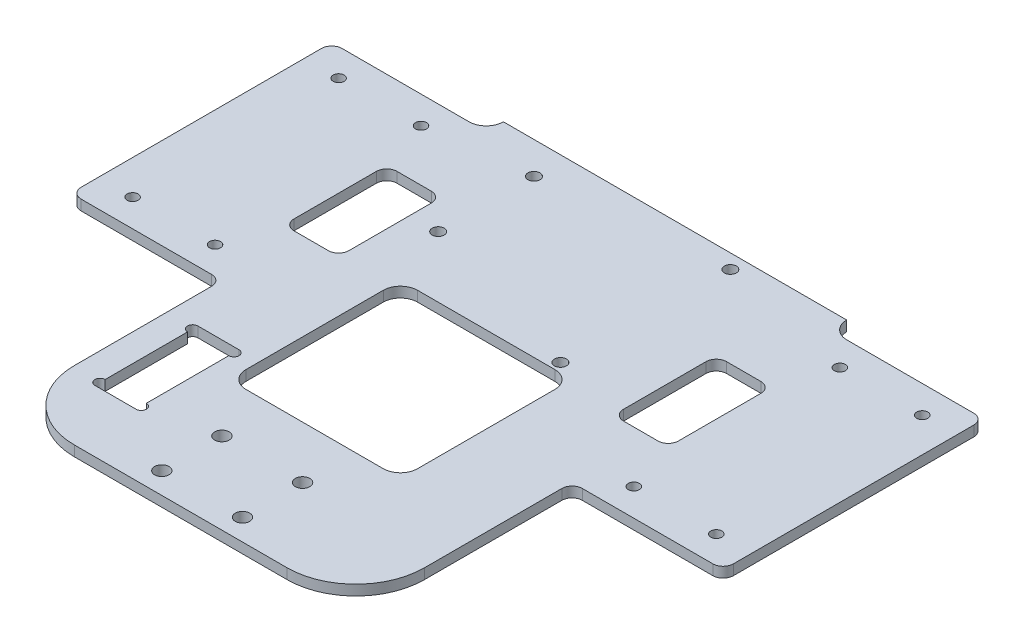
SolidWorks part; units mm, degrees
ref_plane "前视基准面" through (0, 0, 0) normal (0, 0, 1) x (1, 0, 0)
ref_plane "上视基准面" through (0, 0, 0) normal (0, 1, 0) x (1, 0, 0)
ref_plane "右视基准面" through (0, 0, 0) normal (1, 0, 0) x (0, 0, -1)
other "Configuration Table"
sketch "草图1" plane through (0, 0, 0) normal (0, 1, 0) x (1, 0, 0)
  line L0 (-31, 0) -> (31, 0)
  line L1 (-95, 66) -> (-95, 136)
  line L2 (-92, 139) -> (92, 139)
  line L3 (95, 136) -> (95, 66)
  line L4 (-11.75, 6.25) -> (11.75, 6.25) construction
  line L5 (0, 0) -> (0, 71) construction
  line L6 (0, 71) -> (-61, 71) construction
  line L7 (-53, 116) -> (-43, 116)
  line L8 (-56, 113) -> (-56, 89)
  line L9 (-53, 86) -> (-43, 86)
  line L11 (-40, 113) -> (-40, 89)
  line L12 (40, 113) -> (40, 89)
  line L13 (53, 86) -> (43, 86)
  line L14 (56, 113) -> (56, 89)
  line L15 (53, 116) -> (43, 116)
  line L16 (-92, 63) -> (-54, 63)
  line L19 (54, 63) -> (92, 63)
  line L20 (51, 20) -> (51, 60)
  line L21 (-51, 20) -> (-51, 60)
  line L23 (-20, 89) -> (20, 89)
  line L24 (-25, 84) -> (-25, 44)
  line L25 (-20, 39) -> (20, 39)
  line L26 (25, 84) -> (25, 44)
  circle A0 centre (-11.75, 23.75) radius 2.1
  circle A1 centre (11.75, 23.75) radius 2.1
  circle A2 centre (11.75, 6.25) radius 2.1
  circle A3 centre (-11.75, 6.25) radius 2.1
  circle A4 centre (-61, 71) radius 1.6
  circle A5 centre (-61, 131) radius 1.6
  circle A6 centre (-85, 131) radius 1.6
  circle A7 centre (-85, 71) radius 1.6
  arc A8 (-43, 116) -> (-40, 113) centre (-43, 113) cw
  arc A9 (-43, 86) -> (-40, 89) centre (-43, 89) ccw
  arc A10 (-56, 89) -> (-53, 86) centre (-53, 89) ccw
  arc A11 (-53, 116) -> (-56, 113) centre (-53, 113) ccw
  arc A12 (53, 116) -> (56, 113) centre (53, 113) cw
  arc A13 (56, 89) -> (53, 86) centre (53, 89) cw
  arc A14 (43, 86) -> (40, 89) centre (43, 89) cw
  arc A15 (43, 116) -> (40, 113) centre (43, 113) ccw
  circle A16 centre (85, 71) radius 1.6
  circle A17 centre (85, 131) radius 1.6
  circle A18 centre (61, 131) radius 1.6
  circle A19 centre (61, 71) radius 1.6
  arc A20 (92, 63) -> (95, 66) centre (92, 66) ccw
  arc A21 (92, 139) -> (95, 136) centre (92, 136) cw
  arc A22 (-95, 136) -> (-92, 139) centre (-92, 136) cw
  arc A23 (-92, 63) -> (-95, 66) centre (-92, 66) cw
  arc A32 (54, 63) -> (51, 60) centre (54, 60) ccw
  arc A33 (-54, 63) -> (-51, 60) centre (-54, 60) cw
  arc A34 (20, 89) -> (25, 84) centre (20, 84) cw
  arc A35 (20, 39) -> (25, 44) centre (20, 44) ccw
  arc A36 (-25, 44) -> (-20, 39) centre (-20, 44) ccw
  arc A37 (-20, 89) -> (-25, 84) centre (-20, 84) ccw
  arc A38 (31, 0) -> (51, 20) centre (31, 20) ccw
  arc A39 (-31, 0) -> (-51, 20) centre (-31, 20) cw
  point P1 (0, 0)
  point P4 (0, 6.25)
  point P32 (-40, 116)
  point P37 (-56, 86)
  point P40 (-56, 116)
  point P61 (56, 116)
  point P62 (56, 86)
  point P63 (40, 116)
  point P68 (0, 89)
  point P69 (0, 139)
  point P70 (25, 64)
  point P76 (95, 139)
  point P79 (-95, 139)
  point P84 (51, 63)
  point P88 (-51, 63)
  point P92 (25, 89)
  point P99 (-25, 89)
  point P102 (51, 0)
  point P105 (-51, 0)
  dimension "D1" = 4.2
  dimension "D4" = 17.5
  dimension "D5" = 3.2
  dimension "D15" = 3
  dimension "D22" = 3
  dimension "D23" = 75
  dimension "D24" = 50
  dimension "D25" = 3
  dimension "D20" = 102
  dimension "D26" = 5
  dimension "D27" = 20
  dimension "D2" = 23.5
  dimension "D3" = 6.25
  dimension "D6" = 24
  dimension "D7" = 60
  dimension "D8" = 61
  dimension "D9" = 102
  dimension "D10" = 190
  dimension "D11" = 30
  dimension "D12" = 16
  dimension "D13" = 0
  dimension "D14" = 40
  dimension "D16" = 8
  dimension "D17" = 8
  dimension "D18" = 139
  dimension "D19" = 8
  dimension "D21" = 15
extrude "凸台-拉伸1" add sketch "草图1" along normal blind 3
sketch "草图4" plane through (0, 0, -139) normal (0, 0, -1) x (-1, 0, 0)
  line L0 (0, 0) -> (0, 3)
  line L1 (-92, 0) -> (92, 0) construction
  line L2 (-92, 3) -> (92, 3) construction
  line L4 (50, 3) -> (-50, 3)
  line L5 (50, 3) -> (50, 0)
  line L6 (50, 0) -> (-50, 0)
  line L7 (-50, 3) -> (-50, 0)
  line L8 (50, 3) -> (-50, 0) construction
  line L9 (50, 0) -> (-50, 3) construction
  point P6 (0, 1.5)
  line M5 (-92, 0) -> (92, 0)
  line M7 (92, 3) -> (-92, 3)
  dimension "D1" = 100
extrude "凸台-拉伸2" add sketch "草图4" along normal blind 5 contours L5 L0 M7 M5
fillet "圆角1" radius 5 2 edges at (50, 1.5, -139) (-50, 1.5, -139)
hole_wizard "孔1" positions "草图2" profile "草图3" legacy
sketch "草图2" plane through (0, 3, 0) normal (0, 1, 0) x (1, 0, 0)
  point P0 (-31.8, 134.7)
  point P2 (-31.8, 106.8)
  point P4 (19, 91.6)
  point P6 (20.3, 139.8)
sketch "草图3" plane through (-31.8, 3, -134.7) normal (1, 0, 0) x (0, 0, 1)
  line L0 (0, 0) -> (0, 100)
  line L1 (0, 100) -> (1.75, 100)
  line L2 (1.75, 100) -> (1.75, 0)
  line L3 (1.75, 0) -> (0, 0)
  line L4 (0, 110) -> (0, -10) construction
  dimension "直径" = 3.5
  dimension "深度" = 100
sketch "草图5" plane through (0, 3, 0) normal (0, 1, 0) x (1, 0, 0)
  line L0 (-31, 0) -> (31, 0) construction
  line L1 (-31, 18) -> (-43, 18)
  line L2 (-31, 18) -> (-31, 48)
  line L3 (-31, 48) -> (-43, 48)
  line L4 (-43, 18) -> (-43, 48)
  line L5 (-51, 60) -> (-51, 20) construction
  dimension "D1" = 18
  dimension "D2" = 8
  dimension "D3" = 12
  dimension "D4" = 30
extrude "切除-拉伸1" cut sketch "草图5" against normal blind 10
sketch "草图6" plane through (0, 3, 0) normal (0, 1, 0) x (1, 0, 0)
  line L0 (-43, 48) -> (-43, 18) construction
  line L2 (-31, 18) -> (-31, 48) construction
  line L3 (-31, 48) -> (-43, 48) construction
  line L4 (-43, 18) -> (-31, 18) construction
  point P0 (-43, 46.5)
  point P1 (-31, 46.5)
  point P5 (-43, 19.5)
  point P8 (-31, 19.5)
  dimension "D1" = 1.5
  dimension "D2" = 1.5
  dimension "D3" = 1.5
  dimension "D4" = 1.5
sketch "草图7" plane through (0, 3, 0) normal (0, 1, 0) x (1, 0, 0)
  point P0 (-43, 46.5)
  point P3 (-31, 46.5)
  point P6 (-31, 19.5)
  point P9 (-43, 19.5)
hole_wizard "孔2" positions "草图7" profile "草图8" legacy end condition up to next
sketch "草图8" plane through (-43, 3, -46.5) normal (1, 0, 0) x (0, 0, 1)
  line L0 (0, 0) -> (0, 3)
  line L1 (0, 3) -> (1.5, 3)
  line L2 (1.5, 3) -> (1.5, 0)
  line L3 (1.5, 0) -> (0, 0)
  line L4 (0, 110) -> (0, -10) construction
  dimension "直径" = 3
  dimension "深度" = 3
